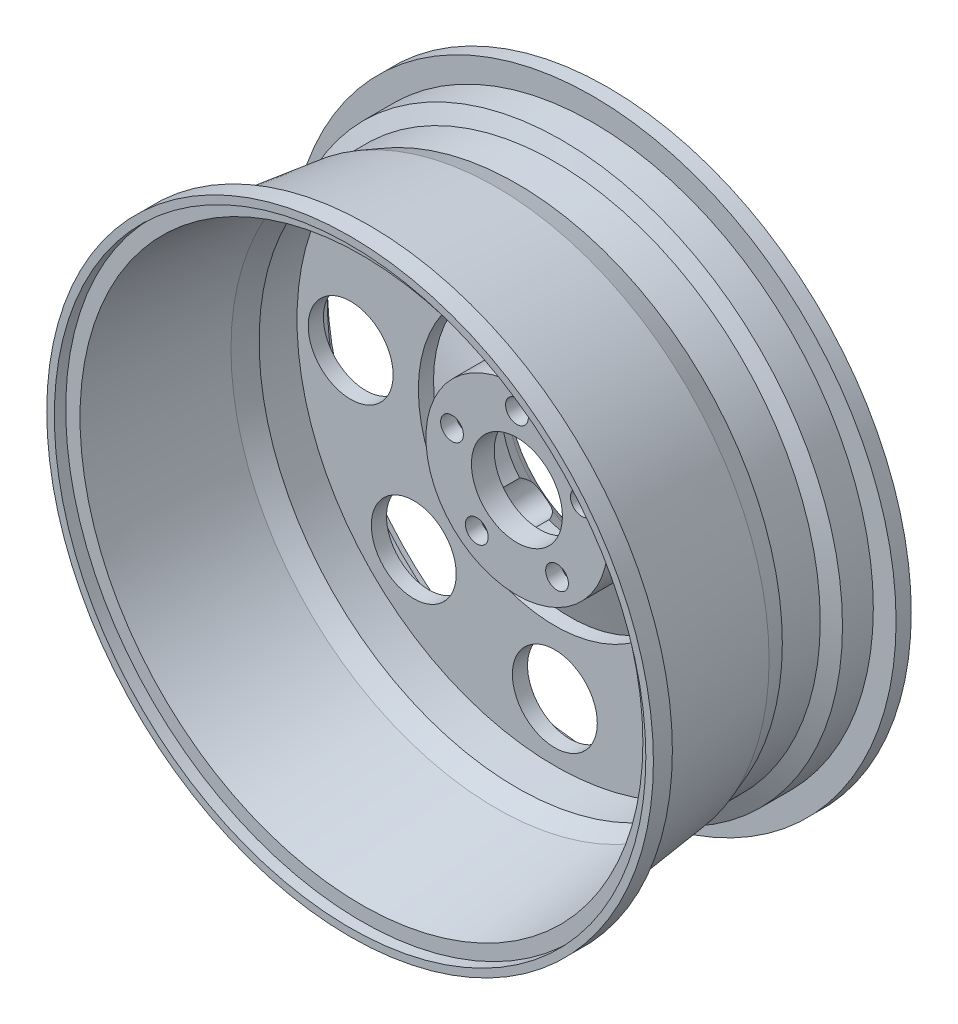
SolidWorks part; units mm, degrees
material "4032-T6"
ref_plane "Front Plane" through (0, 0, 0) normal (0, 0, 1) x (1, 0, 0)
ref_plane "Top Plane" through (0, 0, 0) normal (0, 1, 0) x (1, 0, 0)
ref_plane "Right Plane" through (0, 0, 0) normal (1, 0, 0) x (0, 0, -1)
sketch "Sketch1" plane through (0, 0, 0) normal (1, 0, 0) x (0, 0, -1)
  line L0 (0, 0) -> (0, 241.3) construction
  line L1 (31.75, 38.1) -> (50.8, 38.1)
  line L2 (105.6083, 95.0956) -> (76.2, 114.3)
  line L3 (0, 0) -> (171.9647, 0) construction
  line L4 (31.75, 38.1) -> (31.75, 76.2)
  line L5 (31.75, 76.2) -> (63.5, 76.2)
  line L6 (82.55, 63.5) -> (93.1478, 69.6187)
  line L7 (76.2, 215.9) -> (31.75, 215.9)
  line L8 (31.75, 215.9) -> (14.4879, 222.1829)
  line L9 (14.4879, 222.1829) -> (-98.425, 235.663)
  line L10 (-98.425, 235.663) -> (-98.425, 247.65)
  line L11 (-98.425, 247.65) -> (-107.95, 247.65)
  line L12 (-107.95, 247.65) -> (-107.95, 254)
  line L13 (-107.95, 254) -> (-92.075, 254)
  line L14 (-92.075, 254) -> (-92.075, 241.3)
  line L15 (-92.075, 241.3) -> (14.3035, 228.6)
  line L16 (14.3035, 228.6) -> (31.75, 222.25)
  line L17 (31.75, 222.25) -> (63.5, 222.25)
  line L18 (63.5, 222.25) -> (69.4221, 234.95)
  line L19 (69.4221, 234.95) -> (95.25, 234.95)
  line L20 (95.25, 234.95) -> (95.25, 254)
  line L21 (95.25, 254) -> (107.95, 254)
  line L22 (107.95, 254) -> (107.95, 247.65)
  line L23 (107.95, 247.65) -> (101.6, 247.65)
  line L24 (101.6, 247.65) -> (101.6, 228.6)
  line L25 (101.6, 228.6) -> (88.9, 228.6)
  line L26 (63.5, 76.2) -> (76.2, 114.3)
  line L27 (76.2, 215.9) -> (88.9, 215.9)
  line L28 (82.55, 63.5) -> (50.8, 63.5)
  line L29 (88.9, 215.9) -> (88.9, 228.6)
  line L30 (50.8, 63.5) -> (50.8, 38.1)
  arc A0 (93.1478, 69.6187) -> (105.6083, 95.0956) centre (80.4478, 91.6157) ccw
  point P33 (107.95, 78.1647)
  dimension "D32" = 25.4
  dimension "D2" = 241.3
  dimension "D3" = 228.6
  dimension "D4" = 6.35
  dimension "D5" = 6.35
  dimension "D6" = 38.1
  dimension "D7" = 38.1
  dimension "D8" = 31.75
  dimension "D9" = 31.75
  dimension "D10" = 107.95
  dimension "D11" = 115
  dimension "D12" = 6.35
  dimension "D13" = 31.75
  dimension "D14" = 63.5
  dimension "D15" = 19.05
  dimension "D16" = 12.7
  dimension "D17" = 6.35
  dimension "D18" = 107.95
  dimension "D19" = 6.35
  dimension "D20" = 6.35
  dimension "D21" = 6.35
  dimension "D22" = 9.525
  dimension "D23" = 30
  dimension "D24" = 12.7
  dimension "D25" = 160
  dimension "D26" = 12.7
  dimension "D27" = 14.4879
  dimension "D29" = 101.6
  dimension "D30" = 31.75
  dimension "D31" = 6.35
  dimension "D33" = 19.05
revolve "Revolve1" add sketch "Sketch1" angle 360 about L3
sketch "Sketch2" plane through (0, 0, -50.8) normal (0, 0, -1) x (-1, 0, 0)
  circle A0 centre (0, 57.15) radius 9.525
  circle A1 centre (0, 0) radius 57.15 construction
  circle A2 centre (54.3529, 17.6603) radius 9.525
  circle A3 centre (33.5919, -46.2353) radius 9.525
  circle A4 centre (-33.5919, -46.2353) radius 9.525
  circle A5 centre (-54.3529, 17.6603) radius 9.525
  dimension "D1" = 19.05
  dimension "D2" = 114.3
  dimension "D3" = 5
extrude "Cut-Extrude1" cut sketch "Sketch2" against normal through all and the other way through all
sketch "Sketch3" plane through (0, 0, -50.8) normal (0, 0, -1) x (-1, 0, 0)
  circle A0 centre (0, 57.15) radius 15.875
  circle A1 centre (0, 0) radius 57.15 construction
  circle A2 centre (54.3536, 17.6613) radius 15.875
  circle A3 centre (33.5937, -46.2347) radius 15.875
  circle A4 centre (-33.5901, -46.2359) radius 15.875
  circle A5 centre (-54.3522, 17.6594) radius 15.875
  dimension "D2" = 31.75
  dimension "D1" = 5
extrude "Cut-Extrude2" cut sketch "Sketch3" along normal through all
chamfer "Chamfer1" distance 6.35 angle 45 5 edges at (63.8779, 17.6603, -50.8) (43.1169, -46.2353, -50.8) (-24.0669, -46.2353, -50.8) (-44.8279, 17.6603, -50.8) (9.525, 57.15, -50.8)
sketch "Skizze1" plane through (0, 0, -76.2) normal (0, 0, 1) x (1, 0, 0)
  circle A1 centre (118.11, 118.11) radius 35.56
  circle A2 centre (0, 0) radius 215.9
  circle A3 centre (0, 0) radius 114.3
  circle A4 centre (-118.11, 118.11) radius 35.56
  circle A5 centre (118.11, -118.11) radius 35.56
  circle A6 centre (-118.11, -118.11) radius 35.56
  circle A7 centre (0, 171.9957) radius 35.56
  circle A8 centre (166.1595, 0) radius 35.56
  circle A9 centre (-170.9657, 0) radius 35.56
  circle A10 centre (0, -167.1894) radius 35.56
  circle A11 centre (0, 0) radius 215.9
extrude "Aufsatz-Linear austragen2" add sketch "Skizze1" along normal blind 12.7 contours A5 | A6 | A4 | A1 | A3 | A2 | A10 | A9 | A7 | A8
